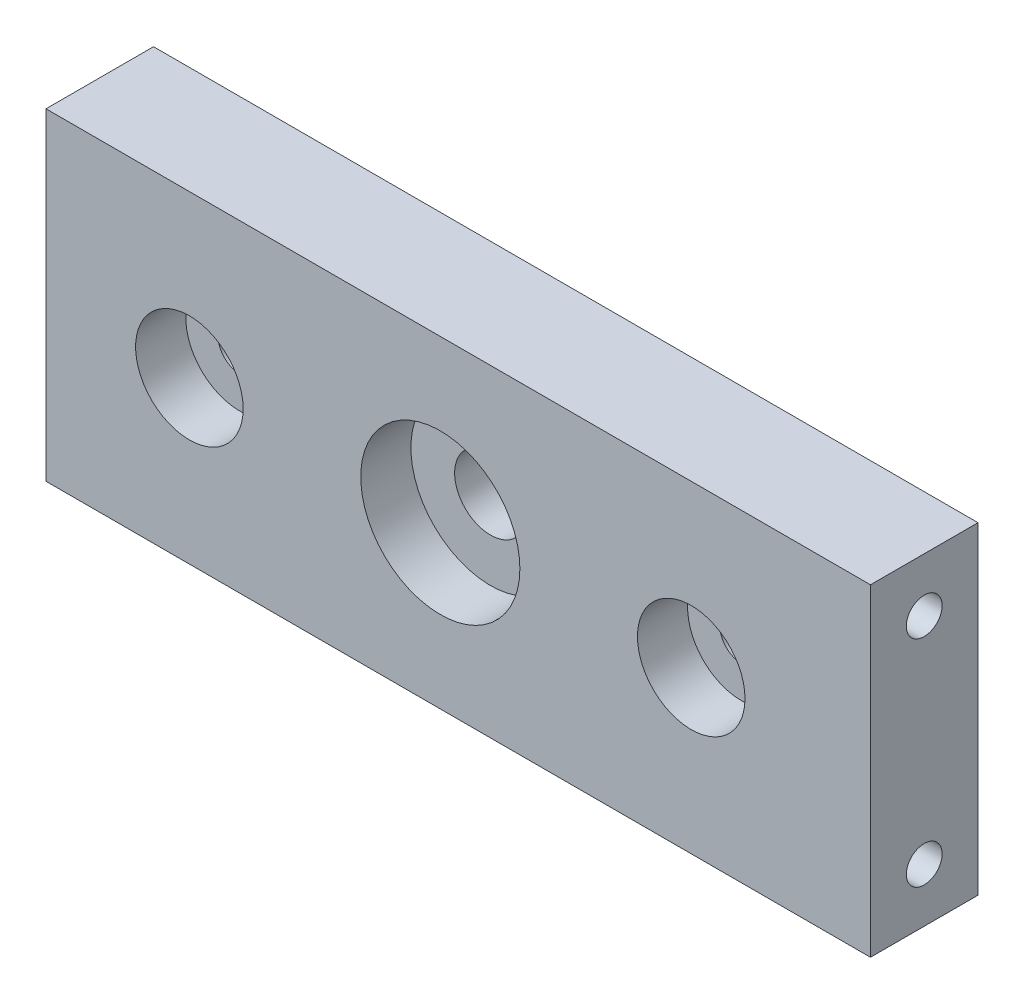
SolidWorks part; units mm, degrees
ref_plane "Front Plane" through (0, 0, 0) normal (0, 0, 1) x (1, 0, 0)
ref_plane "Top Plane" through (0, 0, 0) normal (0, 1, 0) x (1, 0, 0)
ref_plane "Right Plane" through (0, 0, 0) normal (1, 0, 0) x (0, 0, -1)
sketch "Sketch1" plane through (0, 0, 0) normal (0, 0, 1) x (1, 0, 0)
  line L0 (-50, 0) -> (50, 0) construction
  line L1 (50, -22.5) -> (-50, -22.5)
  line L2 (50, -22.5) -> (50, 22.5)
  line L3 (50, 22.5) -> (-50, 22.5)
  line L4 (-50, -22.5) -> (-50, 22.5)
  line L5 (50, -22.5) -> (-50, 22.5) construction
  line L6 (50, 22.5) -> (-50, -22.5) construction
  line L7 (0, 22.5) -> (0, 0) construction
  circle A0 centre (0, 0) radius 5
  circle A1 centre (-35, 0) radius 3
  circle A2 centre (35, 0) radius 3
  point P0 (0, 0)
  dimension "D3" = 6
  dimension "D4" = 10
  dimension "D1" = 100
  dimension "D2" = 45
  dimension "D5" = 15
extrude "Boss-Extrude1" add sketch "Sketch1" along normal blind 15
sketch "Sketch2" plane through (0, 0, 15) normal (0, 0, 1) x (1, 0, 0)
  circle A0 centre (-35, 0) radius 7.5
  circle A1 centre (35, 0) radius 7.5
  circle A2 centre (0, 0) radius 11.1
  dimension "D1" = 15
  dimension "D2" = 15
  dimension "D3" = 22.2
extrude "Cut-Extrude1" cut sketch "Sketch2" against normal blind 7
sketch "Sketch4" plane through (50, 0, 0) normal (1, 0, 0) x (0, 0, -1)
  line L1 (-15, 22.5) -> (0, 22.5)
  line L2 (-15, 22.5) -> (-15, -22.5)
  line L3 (-15, -22.5) -> (0, -22.5)
  line L4 (0, 22.5) -> (0, -22.5)
extrude "Boss-Extrude2" add sketch "Sketch4" along normal blind 10
sketch "Sketch5" plane through (0, 0, 0) normal (0, 0, -1) x (-1, 0, 0)
  circle A0 centre (-35, 0) radius 5.5
  circle A1 centre (35, 0) radius 5.5
  dimension "D1" = 11
  dimension "D2" = 11
extrude "Cut-Extrude2" cut sketch "Sketch5" against normal blind 5
sketch "Sketch7" plane through (-50, 0, 0) normal (-1, 0, 0) x (0, 0, 1)
  line L0 (7.5, 22.5) -> (7.5, -22.5) construction
  line L1 (15, 22.5) -> (0, 22.5) construction
  line L2 (15, -22.5) -> (0, -22.5) construction
  circle A0 centre (7.5, 15) radius 2.5
  circle A1 centre (7.5, -15) radius 2.5
  dimension "D2" = 5
  dimension "D4" = 30
  dimension "D1" = 7.5
  dimension "D3" = 7.5
extrude "Cut-Extrude4" cut sketch "Sketch7" against normal blind 10 and the other way blind 10
sketch "Sketch10" plane through (0, -22.5, 0) normal (0, -1, 0) x (1, 0, 0)
  line L0 (60, 7.5) -> (-50, 7.5) construction
  line L1 (60, 15) -> (60, 0) construction
  line L2 (-50, 15) -> (-50, 0) construction
  circle A0 centre (50, 7.5) radius 2.5
  circle A1 centre (-20, 7.5) radius 2.5
  dimension "D3" = 5
  dimension "D4" = 5
  dimension "D1" = 10
  dimension "D2" = 80
extrude "Cut-Extrude7" cut sketch "Sketch10" against normal blind 10
ref_plane "Plane1" through (5, 0, 0) normal (1, 0, 0) x (0, 0, -1)
mirror "Mirror1" about plane through (5, 0, 0) normal (1, 0, 0) of "Cut-Extrude4"
sketch "Sketch11" plane through (-50, 0, 0) normal (-1, 0, 0) x (0, 0, 1)
  line L1 (0, 22.5) -> (15, 22.5)
  line L2 (0, 22.5) -> (0, -22.5)
  line L3 (0, -22.5) -> (15, -22.5)
  line L4 (15, 22.5) -> (15, -22.5)
  circle A0 centre (7.5, 15) radius 2.5
  circle A1 centre (7.5, -15) radius 2.5
  dimension "D1" = 5
  dimension "D2" = 5
extrude "Boss-Extrude3" add sketch "Sketch11" along normal blind 5
